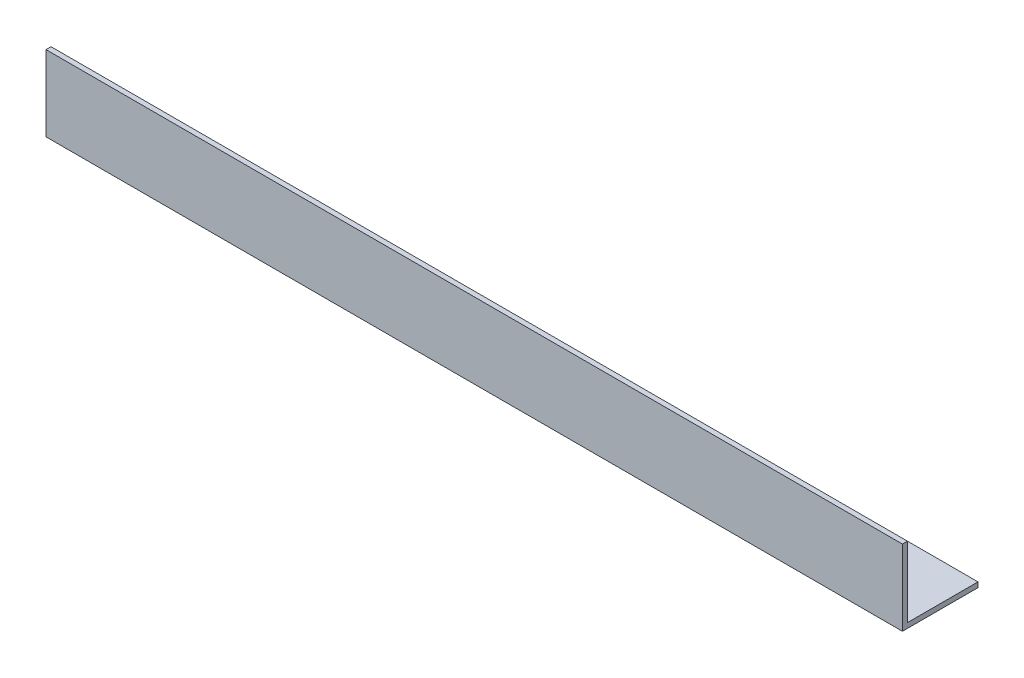
SolidWorks part; units mm, degrees
ref_plane "Спереди" through (0, 0, 0) normal (0, 0, 1) x (1, 0, 0)
ref_plane "Сверху" through (0, 0, 0) normal (0, 1, 0) x (1, 0, 0)
ref_plane "Справа" through (0, 0, 0) normal (1, 0, 0) x (0, 0, -1)
sketch "Эскиз1" plane through (0, 0, 0) normal (1, 0, 0) x (0, 0, -1)
  line L0 (0, 0) -> (0, 45)
  line L1 (0, 0) -> (45, 0)
extrude "Вытянуть-Тонкостенный1" add sketch "Эскиз1" along normal blind 510 thin thin type one direction reverse wall 3
